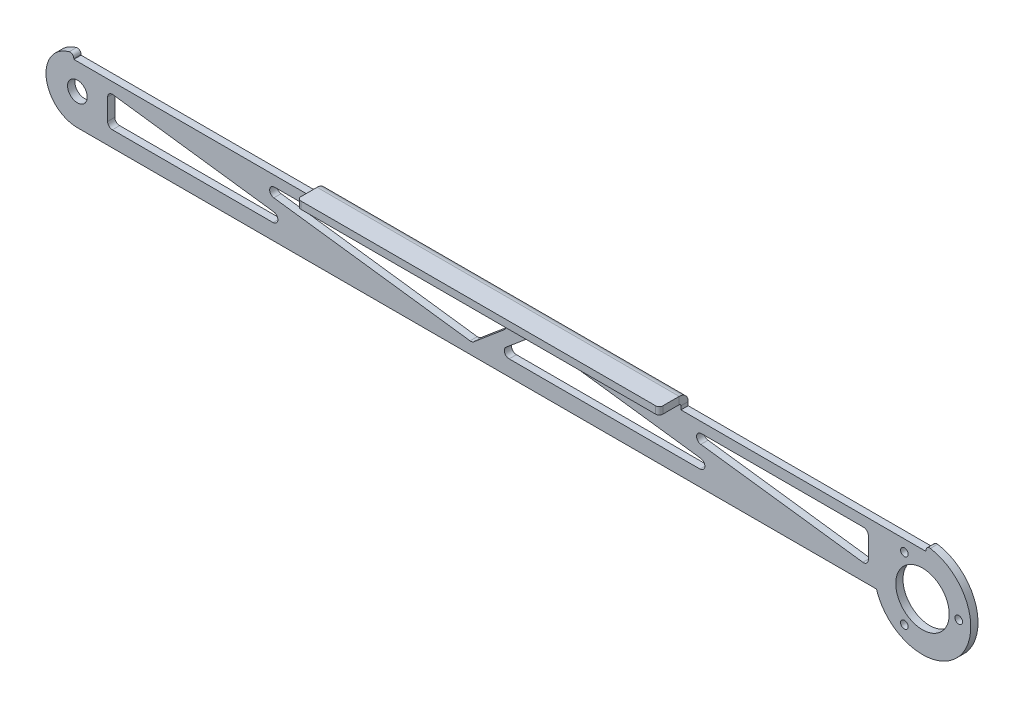
SolidWorks part; units mm, degrees
note: The reader was unsure of these and kept them because the rebuilt part matched: flange length of "Edge-Flange2".
material "6061 Alloy"
ref_plane "Front Plane" through (0, 0, 0) normal (0, 0, 1) x (1, 0, 0)
ref_plane "Top Plane" through (0, 0, 0) normal (0, 1, 0) x (1, 0, 0)
ref_plane "Right Plane" through (0, 0, 0) normal (1, 0, 0) x (0, 0, -1)
sketch "Sketch1" plane through (0, 0, 0) normal (0, 0, 1) x (1, 0, 0)
  line L0 (0, 13) -> (349.93, 13)
  line L1 (55, 0) -> (-55, 0) construction
  line L4 (0, -13) -> (330.8512, -13)
  arc A0 (0, 13) -> (0, -13) centre (0, 0) ccw
  arc A2 (0, -13) -> (0, 13) centre (0, 0) ccw construction
  arc A3 (330.8512, -13) -> (349.93, 13) centre (349.93, -7) ccw
  arc A4 (349.93, 13) -> (330.8512, -13) centre (349.93, -7) ccw construction
  dimension "D1" = 26
  dimension "D2" = 40
  dimension "D3" = 349.93
base flange "Base-Flange1" sketch "Sketch1" thickness 3 reverse thickness direction no parameters "D1"=0.7366
edge flange "Edge-Flange2" sketch "Sketch21" flange angle 90 flange length 12 flange position material outside bend radius 0.7366 thickness 3 relief rectangular parameters "D6"=10
sketch "Sketch21" plane through (0, 13, 0) normal (0, 1, 0) x (-1, 0, 0)
  line L0 (-349.93, 0) -> (0, 0) construction
  line L2 (-349.93, 0) -> (-349.93, 9)
  line L3 (-349.93, 9) -> (0, 9)
  line L4 (0, 9) -> (0, 0)
  line L7 (-349.93, 0) -> (0, 0)
bend "EdgeBend2" bend radius 0.7366 bend angle 90 parameters "D5"=1
sketch "Sketch22" plane through (0, 0, 0) normal (0, 0, 1) x (1, 0, 0)
  circle A0 centre (0, 0) radius 4.075
  circle A1 centre (349.93, -7) radius 11.075
  circle A2 centre (364.93, -7) radius 1.575
  circle A3 centre (342.43, 5.9904) radius 1.575
  circle A4 centre (342.43, -19.9904) radius 1.575
  dimension "D1" = 8.15
  dimension "D2" = 22.15
  dimension "D3" = 3.15
  dimension "D4" = 15
  dimension "D5" = 3
extrude "Cut-Extrude1" cut sketch "Sketch22" against normal through all both and the other way through all normal cut yes
sketch "Sketch23" plane through (0, 0, 0) normal (0, 0, 1) x (1, 0, 0)
  line L0 (12.5, 6.5) -> (12.5, -6.5)
  line L2 (327.5, -6.5) -> (327.5, 6.5)
  line L3 (327.5, 6.5) -> (227.5, 6.5)
  line L5 (50.9615, 6.5) -> (163.4781, -8.2523)
  line L6 (50.9615, 6.5) -> (12.5, 6.5) construction
  line L7 (0, 12.2634) -> (349.93, 12.2634) construction
  line L8 (12.5, 6.5) -> (111.6514, -6.5)
  line L9 (12.5, -6.5) -> (111.6514, -6.5)
  line L10 (173.3081, -6.5) -> (288.7148, -6.5)
  line L11 (180.9615, 6.5) -> (163.4781, -8.2523)
  line L12 (173.3081, -6.5) -> (188.7148, 6.5)
  line L13 (188.7148, 6.5) -> (288.7148, -6.5)
  line L14 (227.5, 6.5) -> (327.5, -6.5)
  line L15 (227.5, 6.5) -> (188.7148, 6.5) construction
  line L16 (180.9615, 6.5) -> (50.9615, 6.5)
  line L19 (188.7148, 6.5) -> (180.9615, 6.5) construction
  point P2 (12.5, 0)
  dimension "D1" = 12.5
  dimension "D2" = 315
  dimension "D3" = 13
  dimension "D4" = 100
  dimension "D5" = 5
  dimension "D6" = 5
  dimension "D7" = 100
  dimension "D8" = 130
  dimension "D9" = 5
extrude "Cut-Extrude2" cut sketch "Sketch23" against normal through all both and the other way through all normal cut yes
fillet "Fillet1" radius 2 14 edges at (12.5, 6.5, -1.5) (288.7148, -6.5, -1.5) (173.3081, -6.5, -1.5) (188.7148, 6.5, -1.5) (163.4781, -8.2523, -1.5) (50.9615, 6.5, -1.5) (180.9615, 6.5, -1.5) (327.5, 6.5, -1.5) (227.5, 6.5, -1.5) (327.5, -6.5, -1.5) (0, 14.5, 9) (349.93, 14.5, 9) (12.5, -6.5, -1.5) (111.6514, -6.5, -1.5)
sketch "Sketch24" plane through (0, 0, 0) normal (0, 0, 1) x (1, 0, 0)
  line L0 (2, 16) -> (347.93, 16) construction
  line L1 (0, 10.7634) -> (100, 10.7634)
  line L2 (0, 10.7634) -> (0, 16)
  line L3 (0, 16) -> (100, 16)
  line L4 (100, 10.7634) -> (100, 16)
  line L5 (0, 10.7634) -> (100, 16) construction
  line L6 (0, 16) -> (100, 10.7634) construction
  line L9 (349.93, 10.7634) -> (249.93, 10.7634)
  line L10 (349.93, 10.7634) -> (349.93, 16)
  line L11 (349.93, 16) -> (249.93, 16)
  line L12 (249.93, 10.7634) -> (249.93, 16)
  line L13 (349.93, 10.7634) -> (249.93, 16) construction
  line L14 (349.93, 16) -> (249.93, 10.7634) construction
  point P4 (50, 13.3817)
  point P12 (299.93, 13.3817)
  dimension "D1" = 100
  dimension "D2" = 100
extrude "Cut-Extrude3" cut sketch "Sketch24" against normal through all both and the other way through all normal cut yes
fillet "Fillet2" radius 1.5 4 edges at (249.93, 14.5, 9) (100, 14.5, 9) (-1.5, 12.9132, -1.5) (351.43, 12.9437, -1.5)
sketch "Bend-Lines1" plane through (0, 0, 0) normal (0, 1, 0) x (1, 0, 0)
sketch "Bounding-Box1" plane through (0, 0, 0) normal (0, 1, 0) x (1, 0, 0)
sheet metal parameters "Sheet-Metal1" thickness 3 parameters "D1"=0.7366
flat pattern "Flat-Pattern1"
sketch "Bend-Lines2" plane through (0, 0, 0) normal (0, 1, 0) x (1, 0, 0)
sketch3d "Bounding-Box2"
  line L0 (-361.91, 34.4982, 0) -> (20.7837, 19.1843, 0) construction
  line L1 (-363.5094, -5.4698, 0) -> (19.1843, -20.7837, 0) construction
  line L2 (-361.91, 34.4982, 0) -> (-363.5094, -5.4698, 0) construction
  line L3 (20.7837, 19.1843, 0) -> (19.1843, -20.7837, 0) construction
sheet metal parameters "Sheet-Metal3" thickness 3 parameters "D1"=0.7366
flat pattern "Flat-Pattern1"
sketch "Bend-Lines2" plane through (0, 0, 0) normal (0, 0, 1) x (1, 0, 0)
  line L0 (350, 14.75) -> (0, 14.75) construction
  line L1 (350, 14.75) -> (0, 14.75) construction
sketch3d "Bounding-Box2"
  line L0 (-361.6909, 39.9734, 0) -> (21.0028, 24.6596, 0) construction
  line L1 (-363.5094, -5.4698, 0) -> (19.1843, -20.7837, 0) construction
  line L2 (-361.6909, 39.9734, 0) -> (-363.5094, -5.4698, 0) construction
  line L3 (21.0028, 24.6596, 0) -> (19.1843, -20.7837, 0) construction
bend of the flat pattern "Flatten-<EdgeBend2>1"
sheet metal parameters "Sheet-Metal4" thickness 3 parameters "D1"=0.7366
flat pattern "Flat-Pattern1"
sketch "Bend-Lines2" plane through (0, 0, 0) normal (0, 0, 1) x (1, 0, 0)
  line L0 (349.93, 14.75) -> (0, 14.75) construction
  line L1 (349.93, 14.75) -> (0, 14.75) construction
sketch3d "Bounding-Box2"
  line L0 (-361.6207, 39.9735, 0) -> (21.003, 24.6594, 0) construction
  line L1 (-363.4395, -5.4697, 0) -> (19.1842, -20.7838, 0) construction
  line L2 (-361.6207, 39.9735, 0) -> (-363.4395, -5.4697, 0) construction
  line L3 (21.003, 24.6594, 0) -> (19.1842, -20.7838, 0) construction
bend of the flat pattern "Flatten-<EdgeBend2>1"
sheet metal parameters "Sheet-Metal5" thickness 3 parameters "D1"=0.7366
flat pattern "Flat-Pattern1"
sketch "Bend-Lines2" plane through (0, 0, 0) normal (0, 0, 1) x (1, 0, 0)
  line L0 (349.93, 14.75) -> (0, 14.75) construction
  line L1 (349.93, 14.75) -> (0, 14.75) construction
sketch3d "Bounding-Box2"
  line L0 (-361.5039, 42.89, 0) -> (21.1197, 27.5759, 0) construction
  line L1 (-363.4395, -5.4697, 0) -> (19.1841, -20.7838, 0) construction
  line L2 (-361.5039, 42.89, 0) -> (-363.4395, -5.4697, 0) construction
  line L3 (21.1197, 27.5759, 0) -> (19.1841, -20.7838, 0) construction
bend of the flat pattern "Flatten-<EdgeBend2>1"
sheet metal parameters "Sheet-Metal6" thickness 3 parameters "D1"=0.7366
flat pattern "Flat-Pattern1"
sketch "Bend-Lines2" plane through (0, 0, 0) normal (0, 0, 1) x (1, 0, 0)
  line L0 (249.93, 14.75) -> (100, 14.75) construction
  line L1 (249.93, 14.75) -> (100, 14.75) construction
sketch3d "Bounding-Box2"
  line L0 (-361.5032, 42.9076, 0) -> (21.1204, 27.5934, 0) construction
  line L1 (-363.4395, -5.4697, 0) -> (19.1841, -20.7838, 0) construction
  line L2 (-361.5032, 42.9076, 0) -> (-363.4395, -5.4697, 0) construction
  line L3 (21.1204, 27.5934, 0) -> (19.1841, -20.7838, 0) construction
bend of the flat pattern "Flatten-<EdgeBend2>1"
